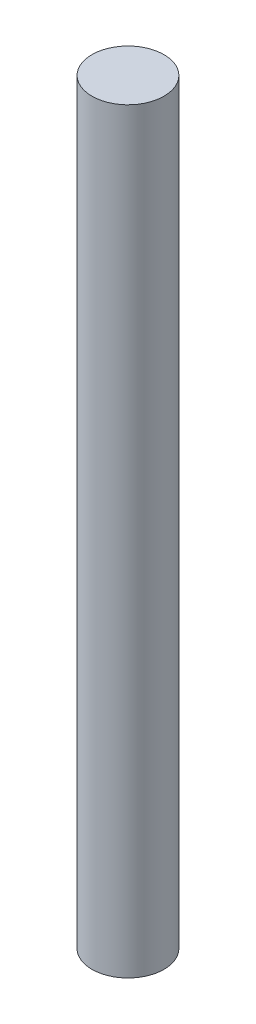
SolidWorks part; units mm, degrees
ref_plane "Front Plane" through (0, 0, 0) normal (0, 0, 1) x (1, 0, 0)
ref_plane "Top Plane" through (0, 0, 0) normal (0, 1, 0) x (1, 0, 0)
ref_plane "Right Plane" through (0, 0, 0) normal (1, 0, 0) x (0, 0, -1)
sketch "Sketch1" plane through (0, 0, 0) normal (0, 1, 0) x (1, 0, 0)
  circle A0 centre (0, 0) radius 4.7625
  dimension "D1" = 9.525
extrude "Boss-Extrude1" add sketch "Sketch1" along normal blind 50 and the other way blind 50
